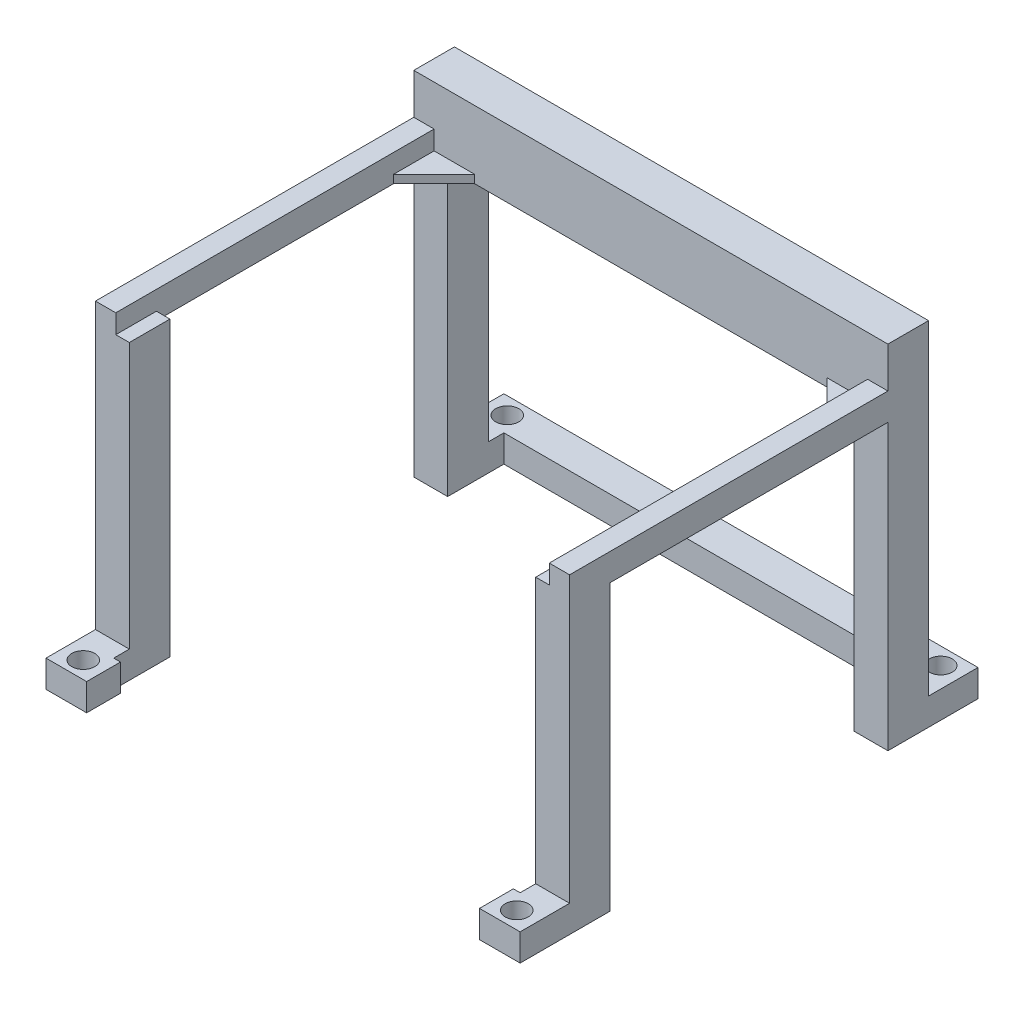
SolidWorks part; units mm, degrees
ref_plane "Front Plane" through (0, 0, 0) normal (0, 0, 1) x (1, 0, 0)
ref_plane "Top Plane" through (0, 0, 0) normal (0, 1, 0) x (1, 0, 0)
ref_plane "Right Plane" through (0, 0, 0) normal (1, 0, 0) x (0, 0, -1)
sketch "Sketch1" plane through (0, 0, 0) normal (0, 1, 0) x (1, 0, 0)
  line L1 (-87.5, 6.25) -> (87.5, 6.25)
  line L3 (-75, -6.25) -> (75, -6.25)
  line L8 (-87.5, -17) -> (-75, -17)
  line L9 (-75, -17) -> (-75, -6.25)
  line L14 (-80, 0) -> (-80, 6.25) construction
  line L15 (-80, 0) -> (-80, -6.25) construction
  line L16 (-80, -6.25) -> (-75, -6.25) construction
  line L17 (87.5, 6.25) -> (87.5, -17)
  line L18 (87.5, -17) -> (75, -17)
  line L19 (-87.5, 6.25) -> (-87.5, -17)
  line L20 (75, -17) -> (75, -6.25)
  line L21 (-80, 0) -> (-87.5, 0) construction
  line L22 (80, 0) -> (87.5, 0) construction
  line L27 (0, 0) -> (0, -6.25) construction
  line L28 (0, 0) -> (0, 6.25) construction
  circle A0 centre (-80, 0) radius 4.25
  circle A2 centre (80, 0) radius 4.25
  point P1 (0, 0)
  point P3 (0, 0)
  point P4 (0, -6.25)
  point P6 (0, 0)
  dimension "D2" = 8.5
  dimension "D1" = 12.5
  dimension "D3" = 175
  dimension "D4" = 23.25
  dimension "D6" = 12.5
  dimension "D7" = 160
extrude "Boss-Extrude1" add sketch "Sketch1" along normal blind 10 contours L20 L18 L17 L1 L19 L8 L9 L3 A2 A0 region at (0, 0, 1.3336)
sketch "Sketch2" plane through (0, 0, 17) normal (0, 0, 1) x (1, 0, 0)
  line L1 (-87.5, 10) -> (-87.5, 0) construction
  line L2 (-87.5, 130) -> (87.5, 130)
  line L6 (-75, 0) -> (-75, 105)
  line L7 (-75, 105) -> (75, 105)
  line L9 (-87.5, 0) -> (-87.5, 130)
  line L10 (-87.5, 0) -> (-75, 0)
  line L11 (55, 0) -> (-55, 0) construction
  line L12 (75, 0) -> (87.5, 0)
  line L13 (87.5, 0) -> (87.5, 130)
  line L14 (75, 105) -> (75, 0)
  line L15 (-75, 10) -> (-75, 0) construction
  line L16 (-87.5, 0) -> (-75, 0) construction
  point P5 (-155, 0.4698)
  line M12 (-75, 0) -> (-75, 10)
  line M14 (-87.5, 10) -> (-87.5, 0)
  dimension "D1" = 105
  dimension "D2" = 25
extrude "Boss-Extrude2" add sketch "Sketch2" against normal blind 5 and the other way blind 10 contours L2 L6 L7 | M14 M12 | L2 L13 L12 L14 L7 L6 L10 L9 region at (0, 127.82, 17)
sketch "Sketch3" plane through (0, 0, 27) normal (0, 0, 1) x (1, 0, 0)
  line L1 (-87.5, 115) -> (87.5, 115)
  line L2 (-87.5, 115) -> (-87.5, 105)
  line L3 (-87.5, 105) -> (87.5, 105)
  line L4 (87.5, 115) -> (87.5, 105)
  line L5 (-75, 105) -> (75, 105) construction
  line L6 (-87.5, 0) -> (-87.5, 130) construction
  line L7 (87.5, 0) -> (87.5, 130) construction
  point P4 (-32.5, 80)
  dimension "D1" = 10
extrude "Boss-Extrude3" add sketch "Sketch3" along normal blind 51.25
mirror "Mirror2" about plane through (0, 0, 78.25) normal (0, 0, 1) of "Boss-Extrude2", "Boss-Extrude1", "Boss-Extrude3"
sketch "Sketch4" plane through (0, 115, 0) normal (0, 1, 0) x (1, 0, 0)
  line L0 (-87.5, -144.5) -> (87.5, -144.5) construction
  line L1 (-87.5, -129.5) -> (-87.5, -27) construction
  line L2 (80, -26.723) -> (87.5, -26.723) construction
  line L3 (87.5, -129.5) -> (87.5, -27) construction
  line L4 (-80, -36.545) -> (-87.5, -36.545) construction
  line L5 (87.5, -27) -> (-87.5, -27) construction
  line L8 (80, -27) -> (-80, -27)
  line L9 (-80, -27) -> (-80, -144.5)
  line L10 (-80, -144.5) -> (80, -144.5)
  line L11 (80, -144.5) -> (80, -27)
  point P16 (80, -40)
  dimension "7,5" = 7.5
extrude "Cut-Extrude1" cut sketch "Sketch4" against normal blind 10 and the other way up to surface (15 mm away) other way up to face at (0, 130, 137)
sketch "Sketch5" plane through (0, 115, 0) normal (0, 1, 0) x (1, 0, 0)
  line L1 (-87.5, -27) -> (87.5, -27)
  line L2 (-87.5, -27) -> (-87.5, -144.5)
  line L3 (-87.5, -144.5) -> (87.5, -144.5)
  line L4 (87.5, -27) -> (87.5, -144.5)
extrude "Cut-Extrude2" cut sketch "Sketch5" along normal up to surface (15 mm away) up to face at (-83.75, 130, 137)
sketch "Sketch6" plane through (0, 105, 0) normal (0, 1, 0) x (1, 0, 0)
  line L0 (-80, -129.5) -> (-80, -144.5) construction
  line L2 (-75, -144.5) -> (-75, -129.5) construction
  line L3 (-75, -129.5) -> (-80, -129.5) construction
  line L4 (75, -129.5) -> (75, -144.5) construction
  line L5 (75, -144.5) -> (80, -144.5) construction
  line L6 (80, -144.5) -> (80, -129.5) construction
  line L7 (80, -129.5) -> (75, -129.5) construction
  line L8 (-80, -129.5) -> (-80, -144.5)
  line L10 (-75, -144.5) -> (-75, -129.5)
  line L11 (-75, -129.5) -> (-80, -129.5)
  line L12 (75, -129.5) -> (75, -144.5)
  line L13 (75, -144.5) -> (80, -144.5)
  line L14 (80, -144.5) -> (80, -129.5)
  line L15 (80, -129.5) -> (75, -129.5)
  line L16 (-80, -27) -> (-65, -27)
  line L17 (-65, -27) -> (-80, -42)
  line L18 (-80, -27) -> (-80, -129.5) construction
  line L19 (-80, -42) -> (-80, -27)
  line L20 (80, -27) -> (65, -27)
  line L21 (75, -27) -> (-75, -27) construction
  line L22 (65, -27) -> (80, -42)
  line L23 (80, -129.5) -> (80, -27) construction
  line L24 (80, -42) -> (80, -27)
  line L25 (-80, -144.5) -> (-75, -144.5)
  dimension "D1" = 15
extrude "Boss-Extrude4" add sketch "Sketch6" along normal blind 3
sketch "Sketch7" plane through (0, 10, 0) normal (0, 1, 0) x (1, 0, 0)
  line L0 (-75, -150.25) -> (75, -150.25) construction
  line L1 (-72.5, -150.25) -> (72.5, -150.25)
  line L2 (-72.5, -150.25) -> (-72.5, -162.75)
  line L3 (-72.5, -162.75) -> (72.5, -162.75)
  line L4 (72.5, -150.25) -> (72.5, -162.75)
  line L5 (-87.5, -162.75) -> (87.5, -162.75) construction
  line L6 (-84.25, -156.5) -> (-87.5, -156.5) construction
  line L7 (-87.5, -162.75) -> (-87.5, -144.5) construction
  line L8 (-75.75, -156.5) -> (-72.5, -156.5) construction
  circle A0 centre (-80, -156.5) radius 4.25 construction
  point P8 (0, -150.25)
extrude "Cut-Extrude3" cut sketch "Sketch7" against normal up to next
